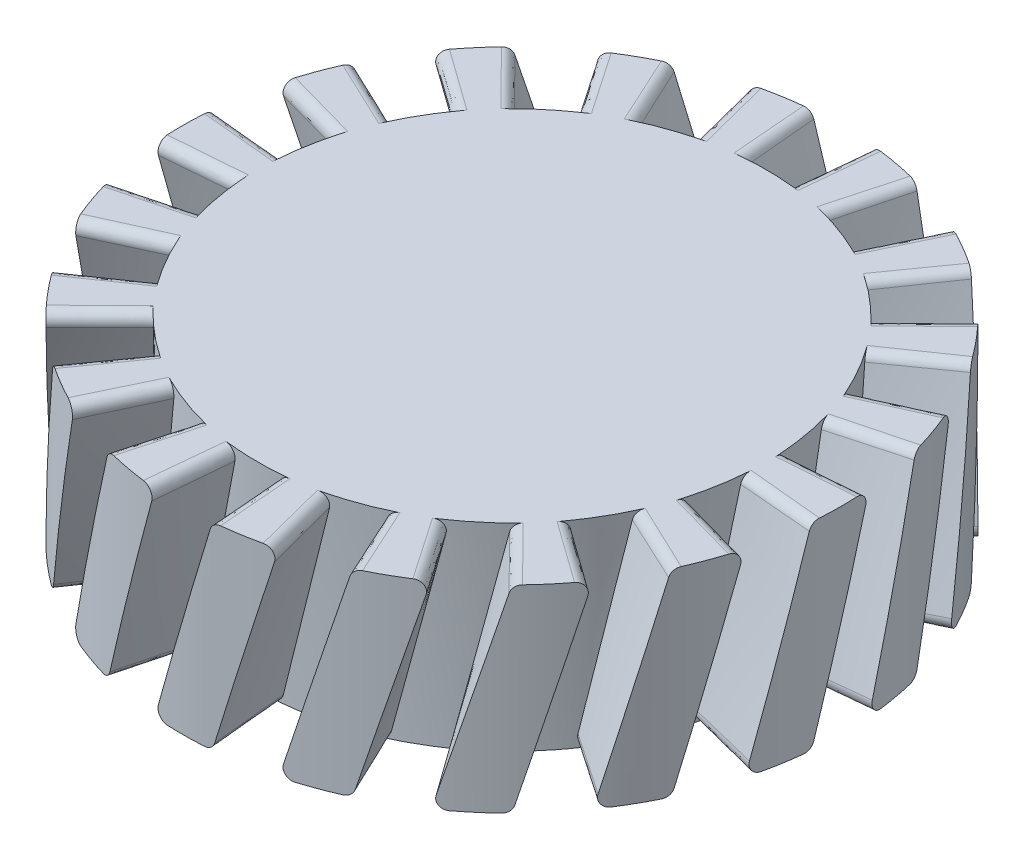
SolidWorks part; units mm, degrees
material "1023 Carbon Steel Sheet (SS)"
ref_plane "Front Plane" through (0, 0, 0) normal (0, 0, 1) x (1, 0, 0)
ref_plane "Top Plane" through (0, 0, 0) normal (0, 1, 0) x (1, 0, 0)
ref_plane "Right Plane" through (0, 0, 0) normal (1, 0, 0) x (0, 0, -1)
sketch "Sketch1" plane through (0, 0, 0) normal (0, 1, 0) x (1, 0, 0)
  circle A0 centre (0, 0) radius 50
  dimension "D1" = 100
extrude "Boss-Extrude1" add sketch "Sketch1" along normal blind 30
sketch "Sketch2" plane through (0, 0, 0) normal (0, 1, 0) x (1, 0, 0)
  circle A0 centre (0, 0) radius 23.5
  dimension "D1" = 47
extrude "Cut-Extrude1" cut sketch "Sketch2" along normal blind 15
ref_axis "Axis1" through (0, -0.7, 0) along (0, 1, 0)
sketch "Sketch4" plane through (0, 0, 0) normal (0, 1, 0) x (1, 0, 0)
  line L0 (0, 0) -> (50, 0) construction
  line L1 (0, 0) -> (49.8097, 4.3578) construction
  line L2 (0, 0) -> (49.8097, -4.3578) construction
  line L3 (38.3535, 3.3555) -> (50.8059, 4.4449)
  line L4 (38.3535, -3.3555) -> (50.8059, -4.4449)
  circle A0 centre (0, 0) radius 50 construction
  arc A1 (38.3535, 3.3555) -> (38.3535, -3.3555) centre (0, 0) cw
  arc A2 (50.8059, 4.4449) -> (50.8059, -4.4449) centre (0, 0) cw
  circle A3 centre (0, 0) radius 23.5 construction
  circle A5 centre (0, 0) radius 50 construction
  dimension "D1" = 10
  dimension "D2" = 15
  dimension "D3" = 1
sketch "Sketch7" plane through (0, 30, 0) normal (0, 1, 0) x (1, 0, 0)
  line L0 (0, 0) -> (49.2404, 8.6824) construction
  line L1 (0, 0) -> (49.8097, 4.3578) construction
  line L2 (0, 0) -> (48.2963, 12.941) construction
  line L3 (0, 0) -> (50, 0) construction
  line L4 (37.1881, 9.9645) -> (49.2622, 13.1998)
  line L5 (38.3535, 3.3555) -> (50.8059, 4.4449)
  circle A0 centre (0, 0) radius 50 construction
  arc A1 (37.1881, 9.9645) -> (38.3535, 3.3555) centre (0, 0) cw
  arc A2 (49.2622, 13.1998) -> (50.8059, 4.4449) centre (0, 0) cw
  arc A3 (50.8059, -4.4449) -> (50.8059, 4.4449) centre (0, 0) ccw construction
  arc A4 (38.3535, -3.3555) -> (38.3535, 3.3555) centre (0, 0) ccw construction
  dimension "D1" = 10
  dimension "D2" = 10
loft "Cut-Loft1" cut profiles "Sketch4", "Sketch7" connector at (50.8059, 0, -4.4449) connector at (49.2622, 30, -13.1998)
fillet "Fillet2" radius 1.5 4 edges at (44.0816, 0, -3.8566)
pattern_circular "CirPattern3" count 18 over 360 about axis through (0, -0.7, 0) along (0, 1, 0) of "Cut-Loft1", "Fillet2"
equation "\"Vane_opening\"= 10"
equation "\"D1@Sketch4\"=\"Vane_opening\""
equation "\"D1@Sketch7\"=\"Vane_opening\""
equation "\"Vane_spacing\"= 180 / \"Vane_opening\""
